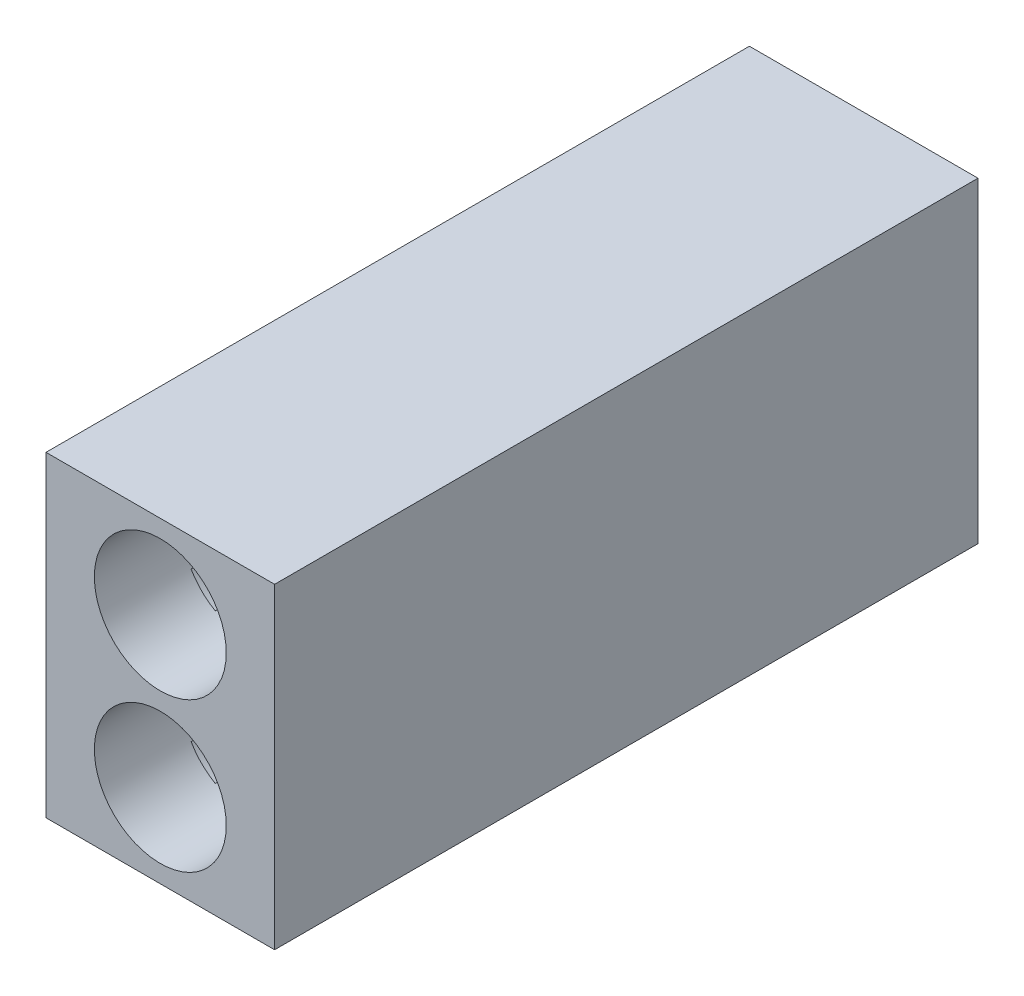
SolidWorks part; units mm, degrees
ref_plane "前基準面" through (0, 0, 0) normal (0, 0, 1) x (1, 0, 0)
ref_plane "上基準面" through (0, 0, 0) normal (0, 1, 0) x (1, 0, 0)
ref_plane "右基準面" through (0, 0, 0) normal (1, 0, 0) x (0, 0, -1)
ref_axis "基準軸1" through (0, -55, 0) along (0, 1, 0)
ref_axis "基準軸2" through (-88.99, 0, 0) along (1, 0, 0)
ref_axis "基準軸3" through (0, 0, 55) along (0, 0, -1)
sketch "草圖1" plane through (0, 0, 0) normal (0, 0, 1) x (1, 0, 0)
  line L1 (-130, 0) -> (0, 0)
  line L2 (-130, 0) -> (-130, 180)
  line L3 (-130, 180) -> (0, 180)
  line L4 (0, 0) -> (0, 180)
  dimension "D1" = 180
  dimension "D2" = 130
extrude "填料-伸長1" add sketch "草圖1" along normal blind 400
sketch "草圖2" plane through (0, 0, 400) normal (0, 0, 1) x (1, 0, 0)
  line L0 (0, 0) -> (0, 180) construction
  line L1 (0, 180) -> (-130, 180) construction
  line L2 (-130, 0) -> (0, 0) construction
  circle A0 centre (-65, 132.5) radius 37.5
  circle A1 centre (-65, 47.5) radius 37.5
  dimension "D4" = 75
  dimension "D5" = 75
  dimension "D1" = 65
  dimension "D2" = 47.5
  dimension "D3" = 47.5
extrude "除料-伸長1" cut sketch "草圖2" against normal through all
sketch "草圖3" plane through (0, 0, 0) normal (0, 0, -1) x (-1, 0, 0)
  line L0 (65, 132.5) -> (125.4016, 237.1186) construction
  line L2 (0, 180) -> (130, 180) construction
  dimension "D1" = 120.8031
  dimension "D2" = 120
ref_plane "平面2" through (0, 0, 5) normal (0, 0, -1) x (-1, 0, 0)
sketch "草圖4" plane through (0, 0, 0) normal (0, 0, -1) x (-1, 0, 0)
  line L0 (65, 132.5) -> (125.4016, 237.1186) construction
  line L1 (86.25, 169.3061) -> (83.75, 164.976)
  line L2 (101.8061, 153.75) -> (97.476, 151.25)
  arc A0 (97.476, 151.25) -> (83.75, 164.976) centre (65, 132.5) ccw
  arc A1 (101.8061, 153.75) -> (86.25, 169.3061) centre (65, 132.5) ccw
  dimension "D1" = 37.5
  dimension "D2" = 42.5
  dimension "D3" = 30
  dimension "D4" = 30
extrude "除料-伸長2" cut sketch "草圖4" against normal blind 350
ref_axis "基準軸4" through (-65, 132.5, 0) along (0, 0, 1)
pattern_circular "環狀複製排列1" count 4 over 360 about axis through (-65, 132.5, 0) along (0, 0, 1) of "除料-伸長2"
ref_plane "平面1" through (0, 90, 0) normal (0, 1, 0) x (1, 0, 0)
mirror "鏡射1" about plane through (0, 90, 0) normal (0, 1, 0) of "環狀複製排列1"
